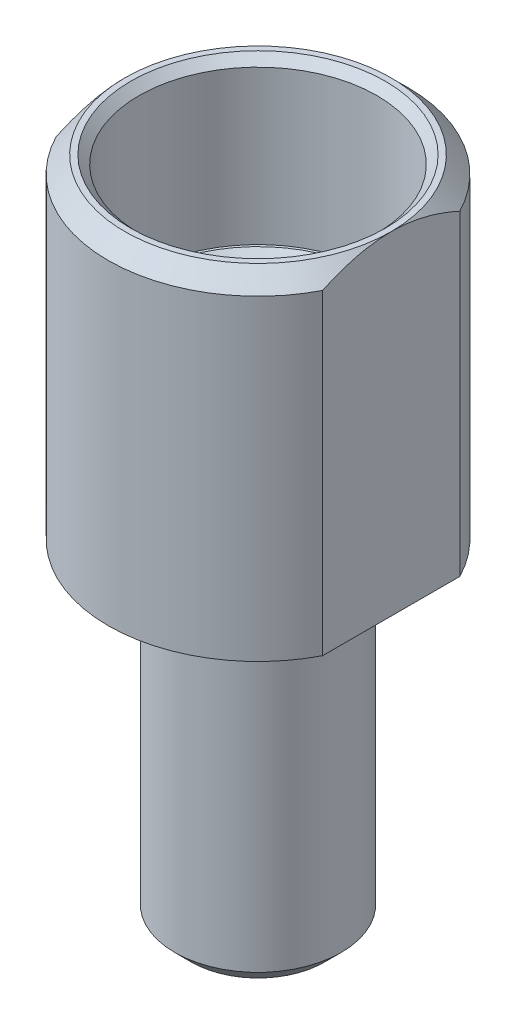
SolidWorks part; units mm, degrees
ref_plane "Plan de face" through (0, 0, 0) normal (0, 0, 1) x (1, 0, 0)
ref_plane "Plan de dessus" through (0, 0, 0) normal (0, 1, 0) x (1, 0, 0)
ref_plane "Plan de droite" through (0, 0, 0) normal (1, 0, 0) x (0, 0, -1)
sketch "Esquisse1" plane through (0, 0, 0) normal (0, 0, 1) x (1, 0, 0)
  line L0 (0, 0) -> (0, 29.7361) construction
  line L1 (3.1, 0) -> (3.1, 10)
  line L2 (2.77, 10) -> (2.77, 22.77)
  line L3 (2.77, 22.77) -> (6.5, 22.77)
  line L4 (6.5, 22.77) -> (6.5, 30.27)
  line L5 (6.5, 30.27) -> (7.15, 30.27)
  line L6 (7.15, 30.27) -> (7.15, 40)
  line L7 (7.15, 40) -> (9, 40)
  line L8 (9, 40) -> (9, 20)
  line L9 (9, 20) -> (7.6, 20)
  line L10 (7.6, 20) -> (7.6, 21.22)
  line L11 (7.6, 21.22) -> (5.5, 21.22)
  line L12 (5.5, 21.22) -> (5.5, 20)
  line L13 (5.5, 20) -> (4.05, 20) construction
  line L14 (4.05, 20) -> (4.05, 18.12) construction
  line L15 (5, 0) -> (3.1, 0)
  line L16 (3.1, 10) -> (2.77, 10)
  line L17 (3.1, 10) -> (2.77, 10)
  line L18 (4.05, 18.12) -> (5, 18.12) construction
  line L19 (5, 18.12) -> (5, 0)
  line L20 (5, 18.12) -> (5, 20)
  line L21 (5, 20) -> (5.5, 20)
  point P25 (6.5, 26.52)
  dimension "D2" = 20
  dimension "D3" = 7.6
  dimension "D4" = 9
  dimension "D5" = 5.5
  dimension "D6" = 4.05
  dimension "D7" = 6.5
  dimension "D8" = 7.15
  dimension "D9" = 9.73
  dimension "D10" = 17.23
  dimension "D11" = 10
  dimension "D12" = 2.77
  dimension "D13" = 1.22
  dimension "D14" = 5
  dimension "1.88" = 1.88
  dimension "D15" = 3.1
  dimension "D16" = 20
  dimension "D17" = 18.12
  dimension "D18" = 10
  dimension "D19" = 7.5
  dimension "D20" = 0.95
revolve "Révolution1" add sketch "Esquisse1" angle 360 about L0 region at (3.5048, 5, 0)
chamfer "Chanfrein3" distance 1 angle 45 1 edges at (0, 40, -9)
sketch "Esquisse2" plane through (0, 40, 0) normal (0, 1, 0) x (1, 0, 0)
  line L0 (0, 0) -> (0, 9) construction
  line L1 (-8, 4.1231) -> (-8, -4.1231)
  line L2 (8, 4.1231) -> (8, -4.1231)
  circle A0 centre (0, 0) radius 9 construction
  arc A1 (-8, 4.1231) -> (-8, -4.1231) centre (0, 0) ccw
  arc A2 (8, 4.1231) -> (8, -4.1231) centre (0, 0) cw
  dimension "D1" = 16
extrude "Enlèv. mat.-Extru.1" cut sketch "Esquisse2" against normal through all
chamfer "Chanfrein4" distance 0.5 angle 45 1 edges at (0, 40, -7.15)
chamfer "Chanfrein5" distance 1.5 angle 45 1 edges at (0, 22.77, -2.77)
chamfer "Chanfrein6" distance 1 angle 45 1 edges at (0, 0, -5)
chamfer "Chanfrein7" distance 0.7 angle 45 1 edges at (0, 0, -3.1)
chamfer "Chanfrein2" distance 0.5 angle 45 2 edges at (0, 10, -2.77) (0, 30.27, -6.5)
